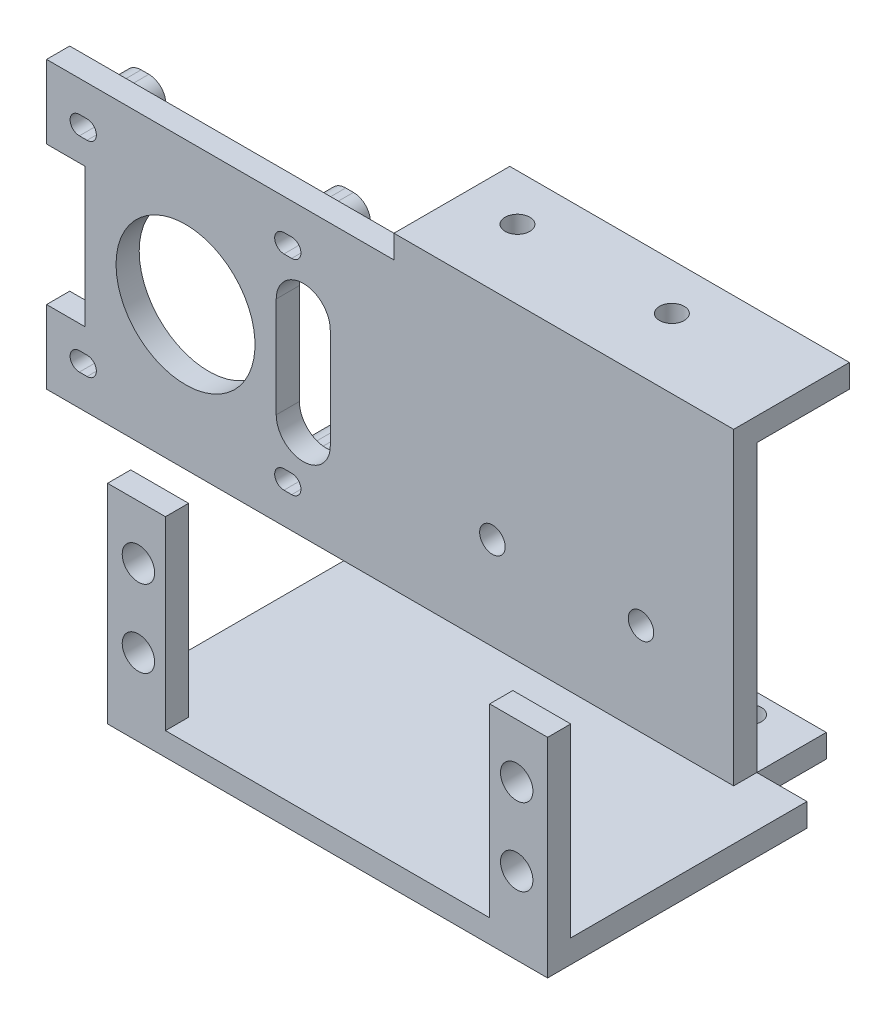
SolidWorks part; units mm, degrees
ref_plane "前视基准面" through (0, 0, 0) normal (0, 0, 1) x (1, 0, 0)
ref_plane "上视基准面" through (0, 0, 0) normal (0, 1, 0) x (1, 0, 0)
ref_plane "右视基准面" through (0, 0, 0) normal (1, 0, 0) x (0, 0, -1)
sketch "草图1" plane through (0, 0, 0) normal (0, 1, 0) x (1, 0, 0)
  line L1 (-28.5, 25.5) -> (28.5, 25.5)
  line L2 (-28.5, 25.5) -> (-28.5, -25.5)
  line L3 (-28.5, -25.5) -> (28.5, -25.5)
  line L4 (28.5, 25.5) -> (28.5, -25.5)
  line L5 (-28.5, 25.5) -> (28.5, -25.5) construction
  line L6 (-28.5, -25.5) -> (28.5, 25.5) construction
  point P0 (0, 0)
  dimension "D1" = 57
  dimension "D2" = 51
extrude "凸台-拉伸1" add sketch "草图1" along normal blind 3
ref_plane "基准面1" through (0, 3, 0) normal (0, 1, 0) x (1, 0, 0)
sketch "草图3" plane through (0, 3, 0) normal (0, 1, 0) x (1, 0, 0)
  line L0 (28.5, 25.5) -> (-28.5, 25.5) construction
  line L1 (-22, 25.5) -> (22, 25.5)
  line L2 (-22, 25.5) -> (-22, 22.5)
  line L3 (-22, 22.5) -> (22, 22.5)
  line L4 (22, 25.5) -> (22, 22.5)
  line L5 (-28.5, 25.5) -> (-28.5, -25.5) construction
  dimension "D1" = 44
  dimension "D2" = 6.5
  dimension "D3" = 3
extrude "凸台-拉伸3" add sketch "草图3" along normal blind 24
sketch "草图5" plane through (0, 3, 0) normal (0, 1, 0) x (1, 0, 0)
  line L0 (28.5, -25.5) -> (28.5, 25.5) construction
  line L1 (-28.5, -5.1) -> (28.5, -5.1)
  line L2 (-28.5, -5.1) -> (-28.5, -8.1)
  line L3 (-28.5, -8.1) -> (28.5, -8.1)
  line L4 (28.5, -5.1) -> (28.5, -8.1)
  line L5 (-28.5, -5.1) -> (28.5, -8.1) construction
  line L6 (-28.5, -8.1) -> (28.5, -5.1) construction
  line L8 (28.5, 25.5) -> (22, 25.5) construction
  line L9 (-28.5, 25.5) -> (-28.5, -25.5) construction
  point P0 (0, -6.6)
  dimension "D1" = 3
  dimension "D2" = 33.6
extrude "凸台-拉伸4" add sketch "草图5" along normal blind 24
ref_plane "基准面3" through (0, 0, 5.1) normal (0, 0, -1) x (-1, 0, 0)
sketch "草图7" plane through (0, 0, 5.1) normal (0, 0, -1) x (-1, 0, 0)
  line L0 (-28.5, 15) -> (28.5, 15) construction
  line L1 (-24.5, 20) -> (24.5, 20) construction
  line L2 (-24.5, 20) -> (-24.5, 10) construction
  line L3 (-24.5, 10) -> (24.5, 10) construction
  line L4 (24.5, 20) -> (24.5, 10) construction
  line L5 (-24.5, 20) -> (24.5, 10) construction
  line L6 (-24.5, 10) -> (24.5, 20) construction
  line L7 (-28.5, 27) -> (-28.5, 3) construction
  line L8 (28.5, 27) -> (28.5, 3) construction
  circle A0 centre (-24.5, 20) radius 2.1
  circle A1 centre (-24.5, 10) radius 2.1
  circle A2 centre (24.5, 20) radius 2.1
  circle A3 centre (24.5, 10) radius 2.1
  point P0 (0, 15)
  dimension "D3" = 4.2
  dimension "D4" = 4.2
  dimension "D5" = 4.2
  dimension "D6" = 4.2
  dimension "D1" = 49
  dimension "D2" = 10
extrude "切除-拉伸1" cut sketch "草图7" against normal blind 3
sketch "草图8" plane through (0, 0, 5.1) normal (0, 0, -1) x (-1, 0, 0)
  line L0 (-22, 27) -> (22, 27) construction
  line L1 (21, 3) -> (-21, 3)
  line L2 (21, 3) -> (21, 27)
  line L3 (21, 27) -> (-21, 27)
  line L4 (-21, 3) -> (-21, 27)
  line L5 (21, 3) -> (-21, 27) construction
  line L6 (21, 27) -> (-21, 3) construction
  point P0 (0, 15)
  dimension "D1" = 42
  dimension "D2" = 24
extrude "切除-拉伸2" cut sketch "草图8" against normal blind 3
ref_plane "基准面4" through (0, 27, 0) normal (0, 1, 0) x (1, 0, 0)
sketch "草图10" plane through (0, 27, 0) normal (0, 1, 0) x (1, 0, 0)
  line L1 (-22, 22.5) -> (22, 22.5)
  line L2 (-22, 22.5) -> (-22, 25.5)
  line L3 (-22, 25.5) -> (22, 25.5)
  line L4 (22, 22.5) -> (22, 25.5)
extrude "凸台-拉伸5" add sketch "草图10" along normal blind 55
ref_plane "基准面5" through (0, 0, -25.5) normal (0, 0, -1) x (-1, 0, 0)
sketch "草图11" plane through (0, 0, -25.5) normal (0, 0, -1) x (-1, 0, 0)
  line L0 (-22, 82) -> (22, 82) construction
  line L1 (-13.2, 85) -> (13.2, 85) construction
  line L2 (-13.2, 85) -> (-13.2, 58.6) construction
  line L3 (-13.2, 58.6) -> (13.2, 58.6) construction
  line L4 (13.2, 85) -> (13.2, 58.6) construction
  line L5 (-13.2, 85) -> (13.2, 58.6) construction
  line L6 (-13.2, 58.6) -> (13.2, 85) construction
  circle A0 centre (-13.2, 85) radius 2.25
  circle A1 centre (13.2, 85) radius 2.25
  circle A2 centre (-13.2, 58.6) radius 2.25
  circle A3 centre (13.2, 58.6) radius 2.25
  point P0 (0, 71.8)
  dimension "D3" = 4.5
  dimension "D4" = 4.5
  dimension "D5" = 4.5
  dimension "D6" = 4.5
  dimension "D1" = 26.4
  dimension "D2" = 26.4
  dimension "D7" = 3
extrude "凸台-拉伸6" add sketch "草图11" against normal blind 8
ref_plane "基准面6" through (0, 0, -22.5) normal (0, 0, 1) x (1, 0, 0)
sketch "草图12" plane through (0, 0, -22.5) normal (0, 0, 1) x (1, 0, 0)
  line L0 (-13.2, 58.6) -> (13.2, 58.6) construction
  line L1 (-10.2, 62.6) -> (2.8, 62.6)
  line L2 (-10.2, 62.6) -> (-10.2, 54.6)
  line L3 (-10.2, 54.6) -> (2.8, 54.6)
  line L4 (2.8, 62.6) -> (2.8, 54.6)
  line L5 (-10.2, 62.6) -> (2.8, 54.6) construction
  line L6 (-10.2, 54.6) -> (2.8, 62.6) construction
  point P0 (-3.7, 58.6)
  dimension "D1" = 8
  dimension "D2" = 13
  dimension "D3" = 3
extrude "切除-拉伸4" cut sketch "草图12" against normal blind 8
ref_plane "基准面7" through (0, 0, -17.5) normal (0, 0, 1) x (1, 0, 0)
sketch "草图13" plane through (0, 0, -17.5) normal (0, 0, 1) x (1, 0, 0)
  circle A0 centre (13.2, 85) radius 1.1
  circle A1 centre (-13.2, 85) radius 1.1
  circle A2 centre (-13.2, 58.6) radius 1.1
  circle A3 centre (13.2, 58.6) radius 1.1
  dimension "D1" = 2.2
  dimension "D2" = 2.2
  dimension "D3" = 2.2
  dimension "D4" = 2.2
extrude "切除-拉伸5" cut sketch "草图13" against normal blind 5
sketch "草图14" plane through (0, 0, -25.5) normal (0, 0, -1) x (-1, 0, 0)
  line L0 (-28.5, 0) -> (28.5, 0) construction
  line L1 (-22, 0) -> (22, 0)
  line L2 (-22, 0) -> (-22, 3)
  line L3 (-22, 3) -> (22, 3)
  line L4 (22, 0) -> (22, 3)
  line L5 (28.05, 3) -> (-28.05, 3) construction
  line L6 (21, 3) -> (28.5, 3) construction
  line L7 (-28.5, 3) -> (-28.5, 0) construction
  dimension "D1" = 44
  dimension "D2" = 6.5
extrude "凸台-拉伸7" add sketch "草图14" along normal blind 6
sketch "草图15" plane through (0, 0, -25.5) normal (0, 0, -1) x (-1, 0, 0)
  line L0 (-22, 82) -> (-22, 3) construction
  line L1 (-22, 43) -> (22, 43)
  line L2 (-22, 43) -> (-22, 40)
  line L3 (-22, 40) -> (22, 40)
  line L4 (22, 43) -> (22, 40)
  line L5 (22, 82) -> (22, 3) construction
  line L7 (-22, 0) -> (22, 0) construction
  dimension "D1" = 40
  dimension "D2" = 3
extrude "凸台-拉伸8" add sketch "草图15" along normal blind 9
ref_plane "基准面8" through (0, 40, 0) normal (0, -1, 0) x (-1, 0, 0)
sketch "草图16" plane through (0, 40, 0) normal (0, -1, 0) x (-1, 0, 0)
  line L0 (22, 31.5) -> (22, 25.5) construction
  line L1 (-22, 31.5) -> (22, 31.5) construction
  circle A0 centre (15, 31.5) radius 1.6
  circle A1 centre (-5, 31.5) radius 1.6
  dimension "D1" = 7
  dimension "D2" = 20
  dimension "D3" = 3.2
  dimension "D4" = 3.2
  dimension "D5" = 0
  dimension "D6" = 0
extrude "切除-拉伸6" cut sketch "草图16" against normal blind 9
sketch "草图17" plane through (0, 0, 0) normal (0, 1, 0) x (1, 0, 0)
  line L0 (-22, 34.5) -> (-22, 25.5) construction
  line L1 (-22, 34.5) -> (22, 34.5) construction
  circle A0 centre (-5, 31.5) radius 1.6
  circle A1 centre (15, 31.5) radius 1.6
  dimension "D1" = 17
  dimension "D2" = 20
  dimension "D3" = 3
  dimension "D4" = 3.2
  dimension "3.2" = 3.2
  dimension "D5" = 3
extrude "切除-拉伸8" cut sketch "草图17" along normal blind 9
sketch "草图18" plane through (0, 3, 0) normal (0, 1, 0) x (1, 0, 0)
  line L1 (-28.5, -25.5) -> (28.5, -25.5)
  line L2 (-28.5, -25.5) -> (-28.5, -43.1)
  line L3 (-28.5, -43.1) -> (28.5, -43.1)
  line L4 (28.5, -25.5) -> (28.5, -43.1)
  dimension "D1" = 17.6
extrude "凸台-拉伸9" add sketch "草图18" against normal blind 3
sketch "草图19" plane through (0, 3, 0) normal (0, 1, 0) x (1, 0, 0)
  line L1 (-28.5, -43.1) -> (28.5, -43.1)
  line L2 (-28.5, -43.1) -> (-28.5, -40.1)
  line L3 (-28.5, -40.1) -> (28.5, -40.1)
  line L4 (28.5, -43.1) -> (28.5, -40.1)
  line L5 (28.5, -43.1) -> (28.5, -8.1) construction
  dimension "D1" = 3
  dimension "D2" = 57
extrude "凸台-拉伸10" add sketch "草图19" along normal blind 25
sketch "草图20" plane through (0, 0, -25.5) normal (0, 0, -1) x (-1, 0, 0)
  line L1 (-29.895, 90.1394) -> (22, 90.1394)
  line L2 (-29.895, 90.1394) -> (-29.895, 43)
  line L3 (-29.895, 43) -> (22, 43)
  line L4 (22, 90.1394) -> (22, 43)
extrude "切除-拉伸9" cut sketch "草图20" against normal blind 10
sketch "草图21" plane through (-28.5, 0, 0) normal (-1, 0, 0) x (0, 0, 1)
  line L9 (43.1, 0) -> (40.1, 0)
  line L10 (43.1, 0) -> (43.1, 32)
  line L11 (43.1, 32) -> (40.1, 32)
  line L12 (40.1, 0) -> (40.1, 32)
  dimension "D1" = 32
  dimension "D2" = 3
extrude "凸台-拉伸11" add sketch "草图21" along normal blind 34
sketch "草图22" plane through (0, 0, 40.1) normal (0, 0, -1) x (-1, 0, 0)
  line L0 (62.5, 32) -> (62.5, 0) construction
  line L1 (33.25, 2.75) -> (59.75, 2.75) construction
  line L2 (33.25, 2.75) -> (33.25, 29.25) construction
  line L3 (33.25, 29.25) -> (59.75, 29.25) construction
  line L4 (59.75, 2.75) -> (59.75, 29.25) construction
  line L5 (33.25, 2.75) -> (59.75, 29.25) construction
  line L6 (33.25, 29.25) -> (59.75, 2.75) construction
  circle A0 centre (59.75, 29.25) radius 1.2
  circle A1 centre (59.75, 2.75) radius 1.2
  circle A2 centre (33.25, 2.75) radius 1.2
  circle A3 centre (33.25, 29.25) radius 1.2
  circle A5 centre (59.75, 2.75) radius 2.25
  circle A6 centre (59.75, 29.25) radius 2.25
  circle A7 centre (33.25, 29.25) radius 2.25
  circle A8 centre (33.25, 2.75) radius 2.25
  point P0 (46.5, 16)
  dimension "D2" = 2.4
  dimension "D3" = 2.4
  dimension "D4" = 2.4
  dimension "D5" = 2.4
  dimension "D6" = 4.5
  dimension "D8" = 4.5
  dimension "D9" = 4.5
  dimension "D10" = 4.5
  dimension "D1" = 26.5
  dimension "D7" = 16
extrude "凸台-拉伸12" add sketch "草图22" along normal blind 5
sketch "草图24" plane through (0, 0, 40.1) normal (0, 0, -1) x (-1, 0, 0)
  line L1 (33.25, 29.25) -> (59.75, 29.25) construction
  line L2 (33.25, 29.25) -> (33.25, 2.75) construction
  line L3 (33.25, 2.75) -> (59.75, 2.75) construction
  line L4 (59.75, 29.25) -> (59.75, 2.75) construction
  circle A0 centre (46.5, 16) radius 9
  dimension "D1" = 18
extrude "切除-拉伸11" cut sketch "草图24" against normal blind 5
sketch "草图25" plane through (0, 0, 43.1) normal (0, 0, 1) x (1, 0, 0)
  line L0 (-28.5, 28) -> (-28.5, 32) construction
  line L1 (-62.5, 0) -> (28.5, 0) construction
  circle A0 centre (-9.25, 15) radius 1.65
  circle A1 centre (10, 15) radius 1.65
  dimension "D1" = 3.3
  dimension "D3" = 3.3
  dimension "D4" = 19.25
  dimension "D5" = 15
  dimension "D2" = 19.25
extrude "切除-拉伸12" cut sketch "草图25" against normal blind 10
sketch "草图26" plane through (0, 0, 40.1) normal (0, 0, -1) x (-1, 0, 0)
  circle A1 centre (33.25, 2.75) radius 1.1
  circle A2 centre (33.25, 29.25) radius 1.2 construction
  circle A3 centre (33.25, 29.25) radius 1.2
  circle A4 centre (59.75, 29.25) radius 1.2 construction
  circle A5 centre (59.75, 29.25) radius 1.2
  circle A6 centre (59.75, 2.75) radius 1.2 construction
  circle A7 centre (59.75, 2.75) radius 1.2
  dimension "D1" = 2.2
extrude "切除-拉伸13" cut sketch "草图26" against normal blind 10
sketch "草图27" plane through (0, 0, 43.1) normal (0, 0, 1) x (1, 0, 0)
  line L0 (-31.25, 9.5) -> (-31.25, 22.5) construction
  line L1 (-46.5, 16) -> (-31.25, 16) construction
  line L2 (-34.75, 9.5) -> (-34.75, 22.5)
  line L3 (-27.75, 9.5) -> (-27.75, 22.5)
  line L5 (-79.3787, 5.5) -> (-58.8487, 5.5)
  line L6 (-79.3787, 5.5) -> (-79.3787, 26.5)
  line L7 (-79.3787, 26.5) -> (-58.8487, 26.5)
  line L8 (-58.8487, 5.5) -> (-58.8487, 26.5)
  line L9 (-79.3787, 5.5) -> (-58.8487, 26.5) construction
  line L10 (-79.3787, 26.5) -> (-58.8487, 5.5) construction
  arc A0 (-34.75, 9.5) -> (-27.75, 9.5) centre (-31.25, 9.5) ccw
  arc A1 (-27.75, 22.5) -> (-34.75, 22.5) centre (-31.25, 22.5) ccw
  circle A2 centre (-33.25, 2.75) radius 1.2 construction
  point P4 (-31.25, 16)
  point P13 (-69.1137, 16)
  dimension "D1" = 3.5
  dimension "D2" = 13
  dimension "D3" = 2
  dimension "D4" = 21
  dimension "D5" = 20.53
extrude "切除-拉伸14" cut sketch "草图27" against normal blind 10
sketch "草图28" plane through (0, 0, 0) normal (0, -1, 0) x (1, 0, 0)
  line L0 (22, -34.5) -> (22, -25.5) construction
  line L1 (-22, -31.5) -> (22, -31.5)
  line L2 (-22, -31.5) -> (-22, -34.5)
  line L3 (-22, -34.5) -> (22, -34.5)
  line L4 (22, -31.5) -> (22, -34.5)
  dimension "D1" = 3
extrude "凸台-拉伸13" add sketch "草图28" against normal blind 3
sketch "草图29" plane through (0, 43, 0) normal (0, 1, 0) x (1, 0, 0)
  line L0 (22, 34.5) -> (22, 22.5) construction
  line L1 (-22, 34.5) -> (22, 34.5)
  line L2 (-22, 34.5) -> (-22, 37.5)
  line L3 (-22, 37.5) -> (22, 37.5)
  line L4 (22, 34.5) -> (22, 37.5)
  dimension "D1" = 3
extrude "凸台-拉伸14" add sketch "草图29" against normal blind 3
sketch "草图30" plane through (0, 0, 0) normal (0, -1, 0) x (1, 0, 0)
  line L0 (16.6, -31.5) -> (13.4, -31.5) construction
  circle A0 centre (15, -31.5) radius 1.6
  circle A1 centre (-5, -31.5) radius 1.6
extrude "切除-拉伸15" cut sketch "草图30" against normal blind 3
sketch "草图32" plane through (0, 3, 0) normal (0, 1, 0) x (1, 0, 0)
  line L1 (28.5, -8.1) -> (-66.4302, -8.1)
  line L2 (28.5, -8.1) -> (28.5, -49.0165)
  line L3 (28.5, -49.0165) -> (-66.4302, -49.0165)
  line L4 (-66.4302, -8.1) -> (-66.4302, -49.0165)
sketch "草图33" plane through (0, 0, -22.5) normal (0, 0, 1) x (1, 0, 0)
  circle A0 centre (-9.25, 15) radius 1.65
  circle A1 centre (10, 15) radius 1.65
extrude "切除-拉伸16" cut sketch "草图33" against normal blind 3
sketch "草图34" plane through (-22, 0, 0) normal (-1, 0, 0) x (0, 0, 1)
  line L0 (-25.5, 1.65) -> (-25.5, -1.65) construction
  line L1 (-25.5, 3) -> (-22.5, 3)
  line L2 (-25.5, 3) -> (-25.5, 40)
  line L3 (-25.5, 40) -> (-22.5, 40)
  line L4 (-22.5, 3) -> (-22.5, 40)
  line L5 (28.05, 3) -> (-28.05, 3) construction
  line L6 (-22.5, -22) -> (-22.5, 22) construction
  line L7 (-6.6, 40) -> (6.6, 40) construction
extrude "凸台-拉伸15" add sketch "草图34" along normal blind 45
sketch "草图35" plane through (0, 0, -25.5) normal (0, 0, -1) x (-1, 0, 0)
  line L0 (61.75, 34.75) -> (62.75, 34.75) construction
  line L1 (35.75, 8.25) -> (62.25, 8.25) construction
  line L2 (35.75, 8.25) -> (35.75, 34.75) construction
  line L3 (35.75, 34.75) -> (62.25, 34.75) construction
  line L4 (62.25, 8.25) -> (62.25, 34.75) construction
  line L5 (35.75, 8.25) -> (62.25, 34.75) construction
  line L6 (35.75, 34.75) -> (62.25, 8.25) construction
  line L7 (67, 40) -> (67, 3) construction
  line L8 (61.75, 35.95) -> (62.75, 35.95)
  line L9 (61.75, 33.55) -> (62.75, 33.55)
  line L10 (61.75, 8.25) -> (62.75, 8.25) construction
  line L11 (61.75, 9.45) -> (62.75, 9.45)
  line L12 (61.75, 7.05) -> (62.75, 7.05)
  line L13 (35.25, 34.75) -> (36.25, 34.75) construction
  line L14 (35.25, 35.95) -> (36.25, 35.95)
  line L15 (35.25, 33.55) -> (36.25, 33.55)
  line L16 (35.25, 8.25) -> (36.25, 8.25) construction
  line L17 (35.25, 9.45) -> (36.25, 9.45)
  line L18 (35.25, 7.05) -> (36.25, 7.05)
  line L19 (-28.5, 3) -> (66.4302, 3) construction
  line L20 (35.25, 36.95) -> (36.25, 36.95)
  line L21 (35.25, 32.55) -> (36.25, 32.55)
  line L22 (61.75, 36.95) -> (62.75, 36.95)
  line L23 (61.75, 32.55) -> (62.75, 32.55)
  line L24 (61.75, 10.45) -> (62.75, 10.45)
  line L25 (61.75, 6.05) -> (62.75, 6.05)
  line L26 (35.25, 10.45) -> (36.25, 10.45)
  line L27 (35.25, 6.05) -> (36.25, 6.05)
  arc A0 (61.75, 35.95) -> (61.75, 33.55) centre (61.75, 34.75) ccw
  arc A1 (62.75, 33.55) -> (62.75, 35.95) centre (62.75, 34.75) ccw
  arc A2 (61.75, 9.45) -> (61.75, 7.05) centre (61.75, 8.25) ccw
  arc A3 (62.75, 7.05) -> (62.75, 9.45) centre (62.75, 8.25) ccw
  arc A4 (35.25, 35.95) -> (35.25, 33.55) centre (35.25, 34.75) ccw
  arc A5 (36.25, 33.55) -> (36.25, 35.95) centre (36.25, 34.75) ccw
  arc A6 (35.25, 9.45) -> (35.25, 7.05) centre (35.25, 8.25) ccw
  arc A7 (36.25, 7.05) -> (36.25, 9.45) centre (36.25, 8.25) ccw
  arc A8 (36.25, 32.55) -> (36.25, 36.95) centre (36.25, 34.75) ccw
  arc A9 (35.25, 36.95) -> (35.25, 32.55) centre (35.25, 34.75) ccw
  arc A10 (62.75, 32.55) -> (62.75, 36.95) centre (62.75, 34.75) ccw
  arc A11 (61.75, 36.95) -> (61.75, 32.55) centre (61.75, 34.75) ccw
  arc A12 (62.75, 6.05) -> (62.75, 10.45) centre (62.75, 8.25) ccw
  arc A13 (61.75, 10.45) -> (61.75, 6.05) centre (61.75, 8.25) ccw
  arc A14 (36.25, 6.05) -> (36.25, 10.45) centre (36.25, 8.25) ccw
  arc A15 (35.25, 10.45) -> (35.25, 6.05) centre (35.25, 8.25) ccw
  circle A16 centre (49, 21.5) radius 9
  point P0 (49, 21.5)
  point P9 (62.25, 34.75)
  point P15 (62.25, 8.25)
  point P22 (35.75, 34.75)
  point P29 (35.75, 8.25)
  dimension "D7" = 1.2
  dimension "D9" = 1.2
  dimension "D11" = 1.2
  dimension "D13" = 18
  dimension "D1" = 26.5
  dimension "D2" = 1.2
  dimension "D3" = 1
  dimension "D4" = 18
  dimension "D5" = 18.5
  dimension "D6" = 1
  dimension "D8" = 1
  dimension "D10" = 1
  dimension "D12" = 1
extrude "凸台-拉伸17" add sketch "草图35" along normal blind 5 contours L20 A9 L21 A8 A5 L15 A4 L14 | L22 A11 L23 A10 A1 L9 A0 L8 | L26 A15 L27 A14 A7 L18 A6 L17 | L24 A13 L25 A12 A3 L12 A2 L11 region at (-35.75, 36.8803, -25.5) region at (-62.25, 36.8803, -25.5) region at (-62.25, 10.3803, -25.5) region at (-35.75, 10.3803, -25.5)
sketch "草图36" plane through (0, 0, -25.5) normal (0, 0, -1) x (-1, 0, 0)
  line L14 (35.25, 7.05) -> (36.25, 7.05) construction
  line L15 (36.25, 9.45) -> (35.25, 9.45) construction
  line L21 (61.75, 7.05) -> (62.75, 7.05) construction
  line L24 (62.75, 9.45) -> (61.75, 9.45) construction
  line L26 (61.75, 33.55) -> (62.75, 33.55) construction
  line L28 (62.75, 35.95) -> (61.75, 35.95) construction
  line L29 (35.25, 33.55) -> (36.25, 33.55) construction
  line L30 (36.25, 35.95) -> (35.25, 35.95) construction
  line L31 (35.25, 7.05) -> (36.25, 7.05)
  line L32 (36.25, 9.45) -> (35.25, 9.45)
  line L33 (61.75, 7.05) -> (62.75, 7.05)
  line L34 (62.75, 9.45) -> (61.75, 9.45)
  line L35 (61.75, 33.55) -> (62.75, 33.55)
  line L36 (62.75, 35.95) -> (61.75, 35.95)
  line L37 (35.25, 33.55) -> (36.25, 33.55)
  line L38 (36.25, 35.95) -> (35.25, 35.95)
  arc A16 (36.25, 7.05) -> (36.25, 9.45) centre (36.25, 8.25) ccw construction
  arc A20 (35.25, 9.45) -> (35.25, 7.05) centre (35.25, 8.25) ccw construction
  arc A21 (62.75, 7.05) -> (62.75, 9.45) centre (62.75, 8.25) ccw construction
  arc A28 (61.75, 9.45) -> (61.75, 7.05) centre (61.75, 8.25) ccw construction
  arc A29 (62.75, 33.55) -> (62.75, 35.95) centre (62.75, 34.75) ccw construction
  arc A30 (61.75, 35.95) -> (61.75, 33.55) centre (61.75, 34.75) ccw construction
  arc A31 (36.25, 33.55) -> (36.25, 35.95) centre (36.25, 34.75) ccw construction
  arc A32 (35.25, 35.95) -> (35.25, 33.55) centre (35.25, 34.75) ccw construction
  arc A33 (36.25, 7.05) -> (36.25, 9.45) centre (36.25, 8.25) ccw
  arc A34 (35.25, 9.45) -> (35.25, 7.05) centre (35.25, 8.25) ccw
  arc A35 (62.75, 7.05) -> (62.75, 9.45) centre (62.75, 8.25) ccw
  arc A36 (61.75, 9.45) -> (61.75, 7.05) centre (61.75, 8.25) ccw
  arc A37 (62.75, 33.55) -> (62.75, 35.95) centre (62.75, 34.75) ccw
  arc A38 (61.75, 35.95) -> (61.75, 33.55) centre (61.75, 34.75) ccw
  arc A39 (36.25, 33.55) -> (36.25, 35.95) centre (36.25, 34.75) ccw
  arc A40 (35.25, 35.95) -> (35.25, 33.55) centre (35.25, 34.75) ccw
extrude "切除-拉伸18" cut sketch "草图36" against normal blind 5
extrude "切除-拉伸19" cut sketch "草图35<4>" against normal blind 5 contours A16 region at (-49, 21.5, -25.5)
sketch "草图35<4>" plane through (0, 0, -25.5) normal (0, 0, -1) x (-1, 0, 0) same geometry as "草图35"
sketch "草图37" plane through (0, 0, -25.5) normal (0, 0, -1) x (-1, 0, 0)
  line L0 (33.75, 15) -> (33.75, 28) construction
  line L1 (33.75, 21.5) -> (67, 21.5) construction
  line L2 (30.25, 15) -> (30.25, 28)
  line L3 (37.25, 15) -> (37.25, 28)
  line L5 (67, 40) -> (67, 3) construction
  line L7 (62, 12.5) -> (72, 12.5)
  line L8 (62, 12.5) -> (62, 30.5)
  line L9 (62, 30.5) -> (72, 30.5)
  line L10 (72, 12.5) -> (72, 30.5)
  line L11 (62, 12.5) -> (72, 30.5) construction
  line L12 (62, 30.5) -> (72, 12.5) construction
  arc A0 (30.25, 15) -> (37.25, 15) centre (33.75, 15) ccw
  arc A1 (37.25, 28) -> (30.25, 28) centre (33.75, 28) ccw
  arc A2 (36.25, 7.05) -> (36.25, 9.45) centre (36.25, 8.25) ccw construction
  point P4 (33.75, 21.5)
  dimension "D2" = 3.5
  dimension "D1" = 13
  dimension "D3" = 2.5
  dimension "D4" = 18
  dimension "D5" = 10
extrude "切除-拉伸20" cut sketch "草图37" against normal blind 5
extrude "切除-拉伸21" cut sketch "草图32" against normal through all both and the other way through all
